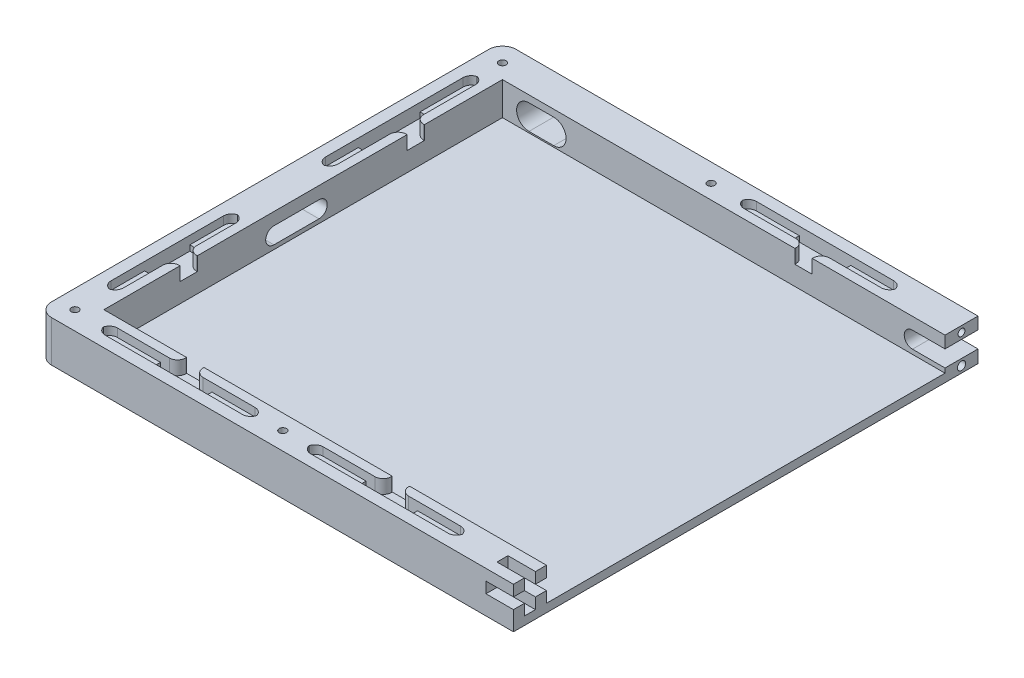
SolidWorks part; units mm, degrees
ref_plane "Front Plane" through (0, 0, 0) normal (0, 0, 1) x (1, 0, 0)
ref_plane "Top Plane" through (0, 0, 0) normal (0, 1, 0) x (1, 0, 0)
ref_plane "Right Plane" through (0, 0, 0) normal (1, 0, 0) x (0, 0, -1)
sketch "Sketch1" plane through (0, 0, 0) normal (0, 1, 0) x (1, 0, 0)
  line L0 (-185.215, 0) -> (43.0487, 0) construction
  line L1 (0, 72.5) -> (-161, 72.5)
  line L2 (0, 215.1028) -> (0, -153.2812) construction
  line L3 (-161, 72.5) -> (-161, -72.5)
  line L4 (-161, -72.5) -> (0, -72.5)
  line L5 (0, 72.5) -> (0, -72.5)
  point P9 (0, 0)
  dimension "D1" = 161
  dimension "D2" = 72.5
extrude "Boss-Extrude1" add sketch "Sketch1" along normal blind 3
sketch "Sketch2" plane through (0, 0, 0) normal (0, 1, 0) x (1, 0, 0)
  line L0 (-224.2217, 0) -> (91.1792, 0) construction
  line L1 (0, 149.3369) -> (0, -151.0656) construction
  line L2 (0, 72.5) -> (0, 84.5)
  line L3 (0, 84.5) -> (-173, 84.5)
  line L4 (-173, 84.5) -> (-173, -84.5)
  line L5 (-173, -84.5) -> (0, -84.5)
  line L6 (0, -84.5) -> (0, -72.5)
  line L8 (-161, 72.5) -> (-161, -72.5) construction
  line L13 (0, -72.5) -> (0, 72.5)
  line L14 (0, 72.5) -> (-161, 72.5)
  line L15 (-161, 72.5) -> (-161, -72.5)
  line L16 (-161, -72.5) -> (0, -72.5)
  line L18 (0, 72.5) -> (-161, 72.5)
  line L19 (-161, 72.5) -> (-161, -72.5)
  line L20 (-161, -72.5) -> (0, -72.5)
  dimension "D1" = 12
  dimension "D2" = 12
  dimension "D3" = 12
  dimension "D4" = 0
extrude "Boss-Extrude2" add sketch "Sketch2" along normal blind 15
sketch "Sketch3" plane through (0, 15, 0) normal (0, 1, 0) x (1, 0, 0)
  line L0 (-161, 72.5) -> (-161, 44.1) construction
  line L1 (-161, -72.5) -> (-161, 72.5) construction
  line L2 (-161, -72.5) -> (-161, -44.8) construction
  line L3 (-161, 44.1) -> (-161, 37.8)
  line L4 (-161, 44.1) -> (-164.3, 44.1)
  line L5 (-161, 37.8) -> (-164.3, 37.8)
  line L6 (-164.3, 44.1) -> (-164.3, 68.95)
  line L7 (-164.3, 37.8) -> (-164.3, 12.95)
  line L8 (-164.3, 68.95) -> (-168.8, 68.95)
  line L9 (-168.8, 68.95) -> (-168.8, 12.95)
  line L10 (-168.8, 12.95) -> (-164.3, 12.95)
  line L11 (-161, 72.5) -> (-161, -72.5) construction
  line L12 (-24.95, -75.8) -> (-49.8, -75.8)
  line L13 (-161, -38.5) -> (-161, -44.8)
  line L14 (-161, -38.5) -> (-164.3, -38.5)
  line L15 (-161, -44.8) -> (-164.3, -44.8)
  line L16 (-164.3, -38.5) -> (-164.3, -18.2)
  line L17 (-164.3, -18.2) -> (-168.8, -18.2)
  line L18 (-168.8, -18.2) -> (-168.8, -65.1)
  line L19 (-168.8, -65.1) -> (-164.3, -65.1)
  line L20 (-164.3, -65.1) -> (-164.3, -44.8)
  line L21 (-24.95, -80.3) -> (-24.95, -75.8)
  line L22 (-80.95, -80.3) -> (-24.95, -80.3)
  line L23 (-80.95, -75.8) -> (-80.95, -80.3)
  line L24 (-56.1, -75.8) -> (-80.95, -75.8)
  line L25 (-56.1, -72.5) -> (-56.1, -75.8)
  line L26 (-49.8, -72.5) -> (-56.1, -72.5)
  line L27 (-49.8, -75.8) -> (-49.8, -72.5)
  line L28 (-99.75, -80.3) -> (-99.75, -75.8)
  line L29 (-155.75, -80.3) -> (-99.75, -80.3)
  line L30 (-155.75, -75.8) -> (-155.75, -80.3)
  line L31 (-130.9, -75.8) -> (-155.75, -75.8)
  line L32 (-130.9, -72.5) -> (-130.9, -75.8)
  line L33 (-124.6, -72.5) -> (-130.9, -72.5)
  line L34 (-124.6, -75.8) -> (-124.6, -72.5)
  line L35 (-99.75, -75.8) -> (-124.6, -75.8)
  line L36 (0, -72.5) -> (-161, -72.5) construction
  line L37 (-161, -72.5) -> (0, -72.5) construction
  line L38 (-48.3, 75.8) -> (-48.3, 72.5)
  line L39 (-23.45, 75.8) -> (-48.3, 75.8)
  line L40 (-23.45, 80.3) -> (-23.45, 75.8)
  line L41 (-79.45, 80.3) -> (-23.45, 80.3)
  line L42 (-79.45, 75.8) -> (-79.45, 80.3)
  line L43 (-54.6, 75.8) -> (-79.45, 75.8)
  line L44 (-54.6, 72.5) -> (-54.6, 75.8)
  line L45 (-48.3, 72.5) -> (-54.6, 72.5)
  line L46 (-161, 72.5) -> (0, 72.5) construction
  dimension "D1" = 28.4
  dimension "D2" = 56
  dimension "D3" = 6.3
  dimension "D4" = 3.3
  dimension "D5" = 6.3
  dimension "D6" = 20.3
  dimension "D7" = 4.5
  dimension "D8" = 4.5
  dimension "D9" = 27.7
  dimension "D10" = 3.3
  dimension "D11" = 30.1
  dimension "D12" = 6.3
  dimension "D13" = 3.3
  dimension "D14" = 4.5
  dimension "D15" = 56
  dimension "D16" = 68.5
  dimension "D17" = 6.3
  dimension "D18" = 3.3
  dimension "D19" = 4.5
  dimension "D20" = 56
  dimension "D21" = 6.3
  dimension "D22" = 3.3
  dimension "D23" = 4.5
  dimension "D24" = 56
  dimension "D25" = 48.3
extrude "Cut-Extrude1" cut sketch "Sketch3" against normal blind 3
sketch "Sketch4" plane through (0, 12, 0) normal (0, 1, 0) x (1, 0, 0)
  line L1 (-54.6, 72.5) -> (-48.3, 72.5)
  line L2 (-48.3, 72.5) -> (-48.3, 75.8)
  line L3 (-48.3, 75.8) -> (-35.875, 75.8) construction
  line L4 (-130.9, -75.8) -> (-143.325, -75.8) construction
  line L5 (-54.6, 75.8) -> (-67.025, 75.8) construction
  line L6 (-79.45, 75.8) -> (-54.6, 75.8) construction
  line L7 (-48.3, 75.8) -> (-23.45, 75.8) construction
  line L10 (-54.6, 72.5) -> (-54.6, 75.8)
  line L14 (-48.3, 75.8) -> (-42.0875, 75.8)
  line L15 (-161, 44.1) -> (-161, 37.8)
  line L16 (-161, 37.8) -> (-164.3, 37.8)
  line L17 (-164.3, 44.1) -> (-164.3, 56.525) construction
  line L18 (-164.3, 44.1) -> (-164.3, 68.95) construction
  line L19 (-164.3, 37.8) -> (-164.3, 25.375) construction
  line L20 (-164.3, 12.95) -> (-164.3, 37.8) construction
  line L21 (-161, 44.1) -> (-164.3, 44.1)
  line L24 (-130.9, -75.8) -> (-155.75, -75.8) construction
  line L26 (-124.6, -75.8) -> (-112.175, -75.8) construction
  line L30 (-164.3, 44.1) -> (-164.3, 50.3125)
  line L31 (-164.3, 50.3125) -> (-168.8, 50.3125)
  line L32 (-168.8, 68.95) -> (-168.8, 12.95) construction
  line L33 (-168.8, 50.3125) -> (-168.8, 27.8502)
  line L34 (-168.8, 68.95) -> (-168.8, 12.95) construction
  line L35 (-168.8, 27.8502) -> (-164.3, 27.8502)
  line L36 (-164.3, 27.8502) -> (-164.3, 37.8)
  line L37 (-164.3, -38.5) -> (-164.3, -28.35) construction
  line L38 (-164.3, -38.5) -> (-164.3, -18.2) construction
  line L39 (-168.8, -33.425) -> (-168.8, -49.875)
  line L40 (-164.3, -65.1) -> (-164.3, -44.8) construction
  line L41 (-164.3, -33.425) -> (-168.8, -33.425)
  line L42 (-168.8, -18.2) -> (-168.8, -65.1) construction
  line L43 (-164.3, -44.8) -> (-164.3, -54.95) construction
  line L44 (-168.8, -49.875) -> (-164.3, -49.875)
  line L45 (-164.3, -49.875) -> (-164.3, -44.8)
  line L46 (-164.3, -44.8) -> (-161, -44.8)
  line L47 (-161, -44.8) -> (-161, -38.5)
  line L48 (-161, -38.5) -> (-164.3, -38.5)
  line L49 (-164.3, -38.5) -> (-164.3, -33.425)
  line L50 (-99.75, -75.8) -> (-124.6, -75.8) construction
  line L51 (-130.9, -72.5) -> (-130.9, -75.8)
  line L52 (-130.9, -75.8) -> (-137.1125, -75.8)
  line L53 (-137.1125, -75.8) -> (-137.1125, -80.3)
  line L54 (-155.75, -80.3) -> (-99.75, -80.3) construction
  line L55 (-137.1125, -80.3) -> (-118.3875, -80.3)
  line L56 (-118.3875, -80.3) -> (-118.3875, -75.8)
  line L59 (-124.6, -72.5) -> (-130.9, -72.5)
  line L60 (-124.6, -72.5) -> (-124.6, -75.8)
  line L61 (-124.6, -75.8) -> (-118.3875, -75.8)
  line L62 (-56.1, -75.8) -> (-68.525, -75.8) construction
  line L63 (-56.1, -75.8) -> (-80.95, -75.8) construction
  line L64 (-49.8, -75.8) -> (-37.375, -75.8) construction
  line L65 (-24.95, -75.8) -> (-49.8, -75.8) construction
  line L66 (-56.1, -75.8) -> (-62.3125, -75.8)
  line L67 (-62.3125, -75.8) -> (-62.3125, -80.3)
  line L68 (-80.95, -80.3) -> (-24.95, -80.3) construction
  line L69 (-62.3125, -80.3) -> (-43.5875, -80.3)
  line L70 (-43.5875, -80.3) -> (-43.5875, -75.8)
  line L71 (-43.5875, -75.8) -> (-49.8, -75.8)
  line L72 (-49.8, -75.8) -> (-49.8, -72.5)
  line L73 (-49.8, -72.5) -> (-56.1, -72.5)
  line L74 (-56.1, -72.5) -> (-56.1, -75.8)
  line L80 (-54.6, 75.8) -> (-60.8125, 75.8)
  line L81 (-60.8125, 75.8) -> (-60.8125, 80.3)
  line L82 (-23.45, 80.3) -> (-79.45, 80.3) construction
  line L83 (-60.8125, 80.3) -> (-42.0875, 80.3)
  line L84 (-23.45, 80.3) -> (-79.45, 80.3) construction
  line L85 (-42.0875, 80.3) -> (-42.0875, 75.8)
extrude "Cut-Extrude2" cut sketch "Sketch4" against normal blind 2
sketch "Sketch5" plane through (-173, 0, 0) normal (-1, 0, 0) x (0, 0, 1)
  line L0 (0, 7.5) -> (32.6582, 7.5) construction
  line L1 (-84.5, 7.5) -> (0, 7.5) construction
  line L2 (-84.5, 15) -> (-84.5, 0) construction
  line L3 (-84.5, 11.8257) -> (-8.75, 11.8257) construction
  line L4 (-5.75, 10.5) -> (10.63, 10.5)
  line L5 (-5.75, 4.5) -> (10.63, 4.5)
  line L8 (-8.75, 4.845) -> (-8.75, 10.155) construction
  arc A0 (-5.75, 4.5) -> (-5.75, 10.5) centre (-5.75, 7.5) cw
  arc A1 (10.63, 10.5) -> (10.63, 4.5) centre (10.63, 7.5) cw
  point P17 (-5.75, 10.5)
  point P21 (-8.75, 7.5)
  dimension "D2" = 3
  dimension "D1" = 16.38
  dimension "D3" = 75.75
extrude "Cut-Extrude3" cut sketch "Sketch5" against normal blind 12
sketch "Sketch7" plane through (0, 0, -84.5) normal (0, 0, -1) x (-1, 0, 0)
  line L0 (60.062, 7.6343) -> (-60.062, 7.6343) construction
  line L1 (0, 0) -> (173, 0) construction
  line L2 (14.8425, 7.6343) -> (14.8425, 12.6467) construction
  line L3 (-4.5375, 10.6343) -> (11.8425, 10.6343)
  line L4 (-4.5375, 4.6343) -> (11.8425, 4.6343)
  line L5 (0, 11.4722) -> (14.8425, 11.4722) construction
  line L6 (0, 15) -> (0, 0) construction
  arc A0 (-4.5375, 4.6343) -> (-4.5375, 10.6343) centre (-4.5375, 7.6343) cw
  arc A1 (11.8425, 10.6343) -> (11.8425, 4.6343) centre (11.8425, 7.6343) cw
  point P3 (0, 7.6343)
  dimension "D3" = 3
  dimension "D1" = 14.8425
  dimension "D2" = 16.38
  dimension "D4" = 7.6343
extrude "Cut-Extrude5" cut sketch "Sketch7" against normal blind 12
sketch "Sketch8" plane through (0, 0, -84.5) normal (0, 0, -1) x (-1, 0, 0)
  line L0 (142.36, 8) -> (151.36, 8) construction
  line L2 (173, 15) -> (173, 0) construction
  line L5 (142.36, 12.5) -> (151.36, 12.5)
  line L6 (142.36, 3.5) -> (151.36, 3.5)
  line L7 (0, 15) -> (173, 15) construction
  arc A0 (142.36, 3.5) -> (142.36, 12.5) centre (142.36, 8) cw
  arc A1 (151.36, 12.5) -> (151.36, 3.5) centre (151.36, 8) cw
  point P0 (146.86, 8)
  dimension "D5" = 9
  dimension "D1" = 26.14
  dimension "D2" = 7
  dimension "D4" = 9
extrude "Cut-Extrude6" cut sketch "Sketch8" against normal blind 20
sketch "Sketch10" plane through (0, 0, 0) normal (1, 0, 0) x (0, 0, -1)
  line L0 (-72.5, 3) -> (-72.5, 15) construction
  line L1 (-72.5, 15) -> (-84.5, 15) construction
  line L2 (-84.5, 15) -> (-84.5, 3) construction
  line L3 (-84.5, 15) -> (-84.5, 0) construction
  line L4 (-84.5, 3) -> (-72.5, 3) construction
  line L5 (-72.5, 3) -> (-84.5, 15) construction
  line L6 (-84.5, 15) -> (-72.5, 15) construction
  line L7 (-72.5, 15) -> (-84.5, 3) construction
  line L8 (-78.5, 15.3824) -> (-78.5, 3) construction
  line L9 (-84.5, 9) -> (-71.292, 9) construction
  line L10 (-80.5, 15) -> (-76.5, 15)
  line L11 (-72.5, 7) -> (-72.5, 11)
  line L12 (-76.5, 3) -> (-80.5, 3)
  line L13 (-84.5, 7) -> (-84.5, 11)
  line L14 (-80.5, 15) -> (-80.5, 11)
  line L15 (-80.5, 11) -> (-84.5, 11)
  line L16 (-84.5, 7) -> (-80.5, 7)
  line L17 (-80.5, 7) -> (-80.5, 3)
  line L18 (-76.5, 3) -> (-76.5, 7)
  line L19 (-76.5, 7) -> (-72.5, 7)
  line L20 (-72.5, 11) -> (-76.5, 11)
  line L21 (-76.5, 11) -> (-76.5, 15)
  line L22 (-78.5, 9) -> (-78.5, 15) construction
  line L23 (-72.5, 9) -> (-84.5, 9) construction
  point P15 (-78.5, 15)
  point P19 (-72.5, 9)
  point P22 (-78.5, 3)
  point P25 (-84.5, 9)
  dimension "D1" = 4
  dimension "D2" = 4
  dimension "D3" = 4
  dimension "D4" = 4
  dimension "D5" = 0
extrude "Cut-Extrude8" cut sketch "Sketch10" against normal blind 10
fillet "Fillet2" radius 5 1 edges at (-173, 7.5, 84.5)
fillet "Fillet3" radius 5 1 edges at (-173, 7.5, -84.5)
sketch "Sketch11" plane through (0, 0, 0) normal (1, 0, 0) x (0, 0, -1)
  line L0 (72.5, 4.6343) -> (84.5, 4.6343) construction
  line L1 (72.5, 4.6343) -> (72.5, 0) construction
  line L2 (-84.5, 0) -> (84.5, 0) construction
  line L3 (72.5, 0) -> (84.5, 0) construction
  line L4 (84.5, 0) -> (84.5, 4.6343) construction
  line L5 (78.5, 4.6343) -> (78.5, 0) construction
  line L6 (72.5, 2.3172) -> (84.5, 2.3172) construction
  line L7 (72.5, 15) -> (72.5, 10.6343) construction
  line L8 (72.5, 10.6343) -> (84.5, 10.6343) construction
  line L9 (84.5, 10.6343) -> (84.5, 15) construction
  line L10 (84.5, 15) -> (72.5, 15) construction
  line L11 (72.5, 15) -> (78.5, 15) construction
  line L12 (78.5, 15) -> (78.5, 10.6343) construction
  line L13 (78.5, 10.6343) -> (72.5, 10.6343) construction
  line L14 (72.5, 10.6343) -> (72.5, 12.8172) construction
  line L15 (72.5, 12.8172) -> (84.5, 12.8172) construction
  circle A0 centre (78.5, 2.3172) radius 1.5
  circle A1 centre (78.5, 12.8172) radius 1.25
  dimension "D1" = 3
  dimension "D2" = 2.5
extrude "Cut-Extrude9" cut sketch "Sketch11" against normal blind 10
sketch "Sketch12" plane through (0, 0, 0) normal (0, -1, 0) x (-1, 0, 0)
  circle A0 centre (166.2678, -77.7678) radius 1.325
  circle A1 centre (90.35, -78.05) radius 1.325
  circle A2 centre (-80.0525, -78.05) radius 1.325
  circle A3 centre (-164.8078, -77.7678) radius 1.325
  circle A4 centre (-164.8078, 77.7678) radius 1.325
  circle A5 centre (-80.0525, 78.05) radius 1.325
  circle A6 centre (90.35, 77.7678) radius 1.325
  circle A7 centre (166.2678, 77.7678) radius 1.325
  circle A9 centre (90.35, -78.05) radius 3
  circle A10 centre (-80.0525, -78.05) radius 3
  circle A11 centre (-164.8078, -77.7678) radius 3
  circle A12 centre (-164.8078, 77.7678) radius 3
  circle A13 centre (-80.0525, 78.05) radius 3
  circle A14 centre (90.35, 77.7678) radius 3
  circle A15 centre (166.2678, 77.7678) radius 3
  circle A16 centre (166.2678, -77.7678) radius 3
  dimension "D1" = 2.65
  dimension "D2" = 2.65
  dimension "D3" = 2.65
  dimension "D4" = 2.65
  dimension "D5" = 2.65
  dimension "D6" = 2.65
  dimension "D7" = 2.65
  dimension "D8" = 2.65
  dimension "D9" = 6
  dimension "D10" = 6
  dimension "D11" = 6
  dimension "D12" = 6
  dimension "D13" = 6
  dimension "D14" = 6
  dimension "D15" = 6
  dimension "D16" = 6
extrude "Cut-Extrude10" cut sketch "Sketch12" against normal blind 17 contours A0 | A1 | A2 | A3 | A4 | A5 | A6 | A7
sketch "Sketch13" plane through (0, 0, 0) normal (0, -1, 0) x (1, 0, 0)
  circle A0 centre (-166.2678, -77.7678) radius 3
  circle A1 centre (-90.35, -77.7678) radius 3
  circle A2 centre (-166.2678, 77.7678) radius 3
  circle A3 centre (-90.35, 78.05) radius 3
  dimension "D1" = 6
  dimension "D2" = 6
  dimension "D3" = 6
  dimension "D4" = 6
extrude "Cut-Extrude11" cut sketch "Sketch13" against normal blind 5
sketch "Sketch14" plane through (0, 0, 0) normal (0, -1, 0) x (-1, 0, 0)
  line L0 (168, -84.5) -> (0, -84.5) construction
  line L1 (173, 79.5) -> (173, -79.5) construction
  line L2 (0, 84.5) -> (168, 84.5) construction
  circle A0 centre (153, -64.5) radius 6.25
  circle A1 centre (153, 64.5) radius 6.25
  point P0 (153, -64.5)
  dimension "D3" = 12.5
  dimension "D4" = 12.5
  dimension "D1" = 20
  dimension "D2" = 20
  dimension "D5" = 20
  dimension "D6" = 20
extrude "Cut-Extrude12" cut sketch "Sketch14" against normal blind 1
fillet "Fillet5" radius 3 10 edges at (-164.3, 12.5, -44.1) (-164.3, 12.5, -37.8) (-164.3, 12.5, 44.8) (-164.3, 12.5, 38.5) (-130.9, 12.5, 75.8) (-124.6, 12.5, 75.8) (-56.1, 12.5, 75.8) (-49.8, 12.5, 75.8) (-54.6, 12.5, -75.8) (-48.3, 12.5, -75.8)
fillet "Fillet6" radius 3 20 edges at (-168.8, 13.5, -12.95) (-164.3, 13.5, -12.95) (-164.3, 13.5, -68.95) (-168.8, 13.5, -68.95) (-168.8, 13.5, 18.2) (-164.3, 13.5, 18.2) (-168.8, 13.5, 65.1) (-164.3, 13.5, 65.1) (-155.75, 13.5, 75.8) (-155.75, 13.5, 80.3) (-99.75, 13.5, 80.3) (-99.75, 13.5, 75.8) (-80.95, 13.5, 80.3) (-80.95, 13.5, 75.8) (-24.95, 13.5, 80.3) (-24.95, 13.5, 75.8) (-23.45, 13.5, -75.8) (-23.45, 13.5, -80.3) (-79.45, 13.5, -75.8) (-79.45, 13.5, -80.3)
